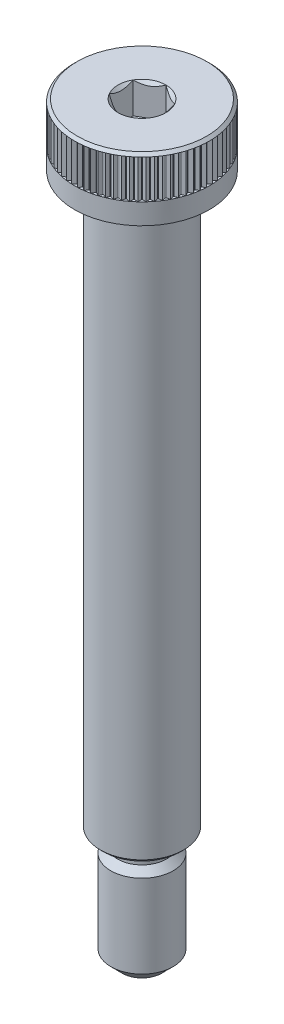
SolidWorks part; units mm, degrees
ref_plane "Front" through (0, 0, 0) normal (0, 0, 1) x (1, 0, 0)
ref_plane "Top" through (0, 0, 0) normal (0, 1, 0) x (1, 0, 0)
ref_plane "Right" through (0, 0, 0) normal (1, 0, 0) x (0, 0, -1)
sketch "Sketch1" plane through (0, 0, 0) normal (0, 1, 0) x (1, 0, 0)
  circle A0 centre (0, 0) radius 6.5
  point P3 (0, -6.5)
  dimension "Head Dia" = 13
extrude "Extrude1" add sketch "Sketch1" along normal blind 6
sketch "Sketch2" plane through (0, 6, 0) normal (0, 1, 0) x (-1, 0, 0)
  line L1 (0, -2.3094) -> (2, -1.1547)
  line L2 (2, -1.1547) -> (2, 1.1547)
  line L3 (2, 1.1547) -> (0, 2.3094)
  line L4 (0, 2.3094) -> (-2, 1.1547)
  line L5 (-2, 1.1547) -> (-2, -1.1547)
  line L6 (-2, -1.1547) -> (0, -2.3094)
  circle A0 centre (0, 0) radius 2 construction
  circle A1 centre (0, 0) radius 6.5 construction
  dimension "Hex Key" = 4
extrude "Cut-Extrude1" cut sketch "Sketch2" against normal blind 3
sketch "Sketch4" plane through (0, 0, 0) normal (0, -1, 0) x (1, 0, 0)
  circle A0 centre (0, 0) radius 4
  circle A1 centre (0, 0) radius 6.5 construction
  dimension "Shoulder Dia" = 8
extrude "Extrude2" add sketch "Sketch4" along normal blind 55
sketch "Sketch5" plane through (0, -55, 0) normal (0, -1, 0) x (1, 0, 0)
  circle A0 centre (0, 0) radius 3
  circle A1 centre (0, 0) radius 4 construction
  dimension "Thread Dia" = 6
extrude "Extrude3" add sketch "Sketch5" along normal blind 11
chamfer "Chamfer1" distance 1.1 angle 45 1 edges at (0, -66, -3)
sketch "Sketch12" plane through (0, -66, 0) normal (0, -1, 0) x (1, 0, 0)
  circle A0 centre (0, 0) radius 3
  circle A1 centre (0, 0) radius 3 construction
curve "Helix/Spiral1" [suppressed] pitch 1 height 11 turns 11 parameters "Thread Pitch "=1
sketch "Sketch13" plane through (0, 0, 0) normal (0, 0, 1) x (1, 0, 0)
  line L0 (3, -66) -> (3, -66.875)
  line L1 (3, -66.875) -> (2.3505, -66.5)
  line L2 (2.3505, -66.5) -> (2.3505, -66.375)
  line L3 (2.3505, -66.375) -> (3, -66)
  line L4 (3, -66.4375) -> (2.3505, -66.4375) construction
  line L5 (3, -64.9) -> (3, -55) construction
  line L6 (2.6752, -66.1875) -> (2.6752, -66.6875) construction
  line L7 (-1.9, -66) -> (1.9, -66) construction
  dimension "D1" = 60
  dimension "D2" = 0.125
  dimension "D3" = 0.5
sweep "Cut-Sweep1" [suppressed] cut profiles "Sketch13" path "Helix/Spiral1"
sketch "Sketch17" plane through (0, 0, 0) normal (0, 0, 1) x (1, 0, 0)
  line L0 (3, -55) -> (2.3505, -55)
  line L1 (2.3505, -55) -> (2.3505, -56.25)
  line L2 (2.3505, -56.25) -> (3, -56.8995)
  line L3 (3, -56.8995) -> (3, -55)
  line L4 (3, -66) -> (3, -66.875) construction
  line L5 (-4, -55) -> (4, -55) construction
  dimension "D1" = 1.25
  dimension "D2" = 45
revolve "Cut-Revolve8" cut sketch "Sketch17" angle 360 about axis through (0, -55, 0) along (0, 1, 0)
fillet "Fillet1" radius 0.5 1 edges at (0, -55, -2.3505)
chamfer "Chamfer3" distance 0.3333 angle 45 1 edges at (0, -55, -4)
ref_plane "Plane1" through (0, 2, 0) normal (0, 1, 0) x (-1, 0, 0)
sketch "Sketch10" plane through (0, 2, 0) normal (0, 1, 0) x (-1, 0, 0)
  line L0 (0, 0) -> (-6.2349, 0) construction
  line L1 (0, 0) -> (-11.9081, -0.5199) construction
  line L2 (-6.4938, -0.2835) -> (-6.589, -0.2877)
  line L3 (-6.4938, -0.2835) -> (-6.2523, -0.042)
  line L4 (0, 0) -> (-11.9081, 0.5199) construction
  line L5 (-6.2523, 0.042) -> (-6.4938, 0.2835)
  line L6 (-6.589, -0.2877) -> (-6.589, 0.2877)
  line L7 (-6.589, 0.2877) -> (-6.4938, 0.2835)
  line L8 (-6.2349, 0) -> (-6.5, 0) construction
  circle A0 centre (0, 0) radius 6.5 construction
  arc A2 (-6.2523, -0.042) -> (-6.2523, 0.042) centre (-6.2943, 0) ccw
  point P3 (-6.5, 0)
  dimension "D4" = 0.0594
  dimension "D1" = 90
  dimension "D2" = 5
  dimension "D3" = 0.0952
  dimension "D5" = 0.2651
extrude "Cut-Extrude3" cut sketch "Sketch10" along normal offset from surface (3.7349 mm away) 0.2651 up to face at (0, 6, 0)
chamfer "Chamfer2" distance 0.2651 angle 45 1 edges at (0, 6, 6.5)
pattern_circular "CirPattern2" count 72 over 360 about axis through (0, -55, 0) along (0, 1, 0) of "Cut-Extrude3"
sketch "Sketch15" plane through (0, 0, 0) normal (1, 0, 0) x (0, 0, -1)
  line L0 (-3, -55) -> (-3, -66)
  line L1 (3, -66) -> (3, -55)
  line L2 (-3.6667, -55) -> (3.6667, -55) construction
  point P7 (-3, -61.25)
  point P9 (3, -61.25)
  dimension "D1" = 4.75
sketch "Sketch16" plane through (0, 6, 0) normal (0, 1, 0) x (1, 0, 0)
  circle A0 centre (0, 0) radius 2.3094
extrude "Extrude4" cut sketch "Sketch16" against normal through all draft 45
sketch "Sketch18" plane through (0, 6, 0) normal (0, 1, 0) x (1, 0, 0)
  line L0 (6.5, 0) -> (-6.5, 0) construction
  arc A0 (6.4938, -0.2835) -> (6.4938, 0.2835) centre (0, 0) ccw construction
equation "\"D1@Cut-Extrude1\"=\"Head Ht@Extrude1\"/2"
equation "\"D1@Chamfer1\" = \"Thread Length@Extrude3\" * .1"
equation "\"D3@Helix/Spiral1\" = \"Thread Length@Extrude3\""
equation "\"D2@Sketch13\" = \"Thread Pitch @Helix/Spiral1\" * .125"
equation "\"D3@Sketch13\" = \"Thread Pitch @Helix/Spiral1\" * .5"
equation "\"D3@Sketch10\" = \"Head Dia@Sketch1\" * .0073205143"
equation "\"D4@Sketch10\" = \"Head Dia@Sketch1\" * .0045714286"
equation "\"D1@Plane1\" = \"Head Ht@Extrude1\"*2/3"
equation "\"D1@Cut-Extrude3\" = \"D5@Sketch10\""
equation "\"D1@Chamfer2\" = \"D5@Sketch10\""
equation "\"D1@Sketch17\" = \"Thread Pitch @Helix/Spiral1\"*1.25"
equation "\"D1@Fillet1\" = \"Thread Pitch @Helix/Spiral1\"/2"
equation "\"D1@Chamfer3\" = \"Thread Pitch @Helix/Spiral1\"/3"
equation "\"D1@Sketch15\" = \"Thread Pitch @Helix/Spiral1\"*4.750"
